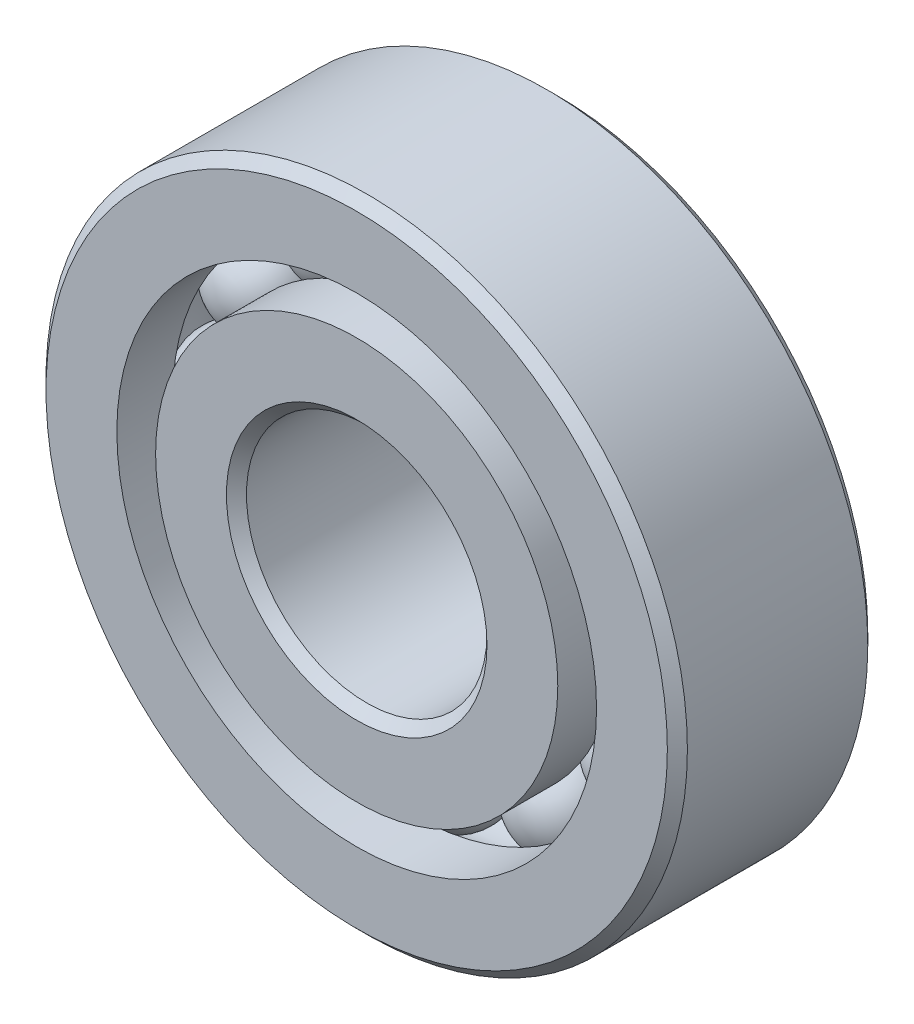
SolidWorks part; units mm, degrees
ref_plane "Front Plane" through (0, 0, 0) normal (0, 0, 1) x (1, 0, 0)
ref_plane "Top Plane" through (0, 0, 0) normal (0, 1, 0) x (1, 0, 0)
ref_plane "Right Plane" through (0, 0, 0) normal (1, 0, 0) x (0, 0, -1)
sketch "Sketch1" plane through (0, 0, 0) normal (1, 0, 0) x (0, 0, -1)
  line L0 (-1.9844, 0) -> (1.9844, 0) construction
  line L1 (0, 6.35) -> (0, -6.35) construction
  line L2 (1.7859, 6.35) -> (-1.7859, 6.35)
  line L3 (-1.7859, 6.35) -> (-1.9844, 6.1516)
  line L4 (-1.9844, 6.1516) -> (-1.9844, 4.7494)
  line L5 (-1.9844, 4.7494) -> (-0.8819, 4.7494)
  line L6 (1.9844, 4.7494) -> (0.8819, 4.7494)
  line L7 (1.9844, 6.1516) -> (1.9844, 4.7494)
  line L8 (1.7859, 6.35) -> (1.9844, 6.1516)
  line L9 (0, 6.35) -> (0, 4.3656) construction
  line L10 (0, 4.3656) -> (0, 2.3813) construction
  arc A0 (-0.8819, 4.7494) -> (0.8819, 4.7494) centre (0, 4.3656) cw
  point P14 (0, 2.3813)
  dimension "Width" = 3.9688
  dimension "OD" = 12.7
  dimension "D1" = 45
  dimension "D2" = 0.1984
  dimension "Shaft Dia" = 4.7625
  dimension "D3" = 1.7639
  dimension "D4" = 0.3838
revolve "Revolve1" add sketch "Sketch1" angle 360 about L0
sketch "Sketch3" plane through (0, 0, 0) normal (1, 0, 0) x (0, 0, -1)
  line L0 (-1.9844, 3.9818) -> (-0.8819, 3.9818)
  line L1 (0, 6.35) -> (0, -6.35) construction
  line L2 (-1.9844, 6.1516) -> (-1.9844, 4.7494) construction
  line L3 (-1.9844, 3.9818) -> (-1.9844, 2.5797)
  line L4 (-1.7859, 6.35) -> (-1.9844, 6.1516) construction
  line L5 (-1.9844, 2.5797) -> (-1.7859, 2.3813)
  line L6 (-1.7859, 2.3813) -> (1.7859, 2.3813)
  line L7 (1.7859, 6.35) -> (1.7859, -6.35) construction
  line L8 (1.7859, 2.3813) -> (1.9844, 2.5797)
  line L9 (1.9844, -6.1516) -> (1.9844, 6.1516) construction
  line L10 (1.9844, 2.5797) -> (1.9844, 3.9818)
  line L11 (1.9844, 3.9818) -> (0.8819, 3.9818)
  line L13 (1.7859, 6.35) -> (1.9844, 6.1516) construction
  arc A0 (0.8819, 4.7494) -> (-0.8819, 4.7494) centre (0, 4.3656) ccw construction
  arc A1 (0.8819, 3.9818) -> (-0.8819, 3.9818) centre (0, 4.3656) cw
revolve "Revolve3" add sketch "Sketch3" angle 360 about L0
sketch "Sketch4" plane through (0, 0, 0) normal (1, 0, 0) x (0, 0, -1)
  line L0 (-0.9618, 4.3656) -> (0.9618, 4.3656)
  arc A2 (-0.9618, 4.3656) -> (0.9618, 4.3656) centre (0, 4.3656) cw
  arc A3 (0.8819, 4.7494) -> (-0.8819, 4.7494) centre (0, 4.3656) ccw construction
revolve "Revolve4" add sketch "Sketch4" angle 360 about L0
ref_axis "Axis1" through (0, 0, -1.9844) along (0, 0, 1)
pattern_circular "CirPattern1" count 12 every 30 about axis through (0, 0, -1.9844) along (0, 0, 1) of bodies 104
equation "\"D2@Sketch1\" = \"Width@Sketch1\"*.05"
equation "\"D3@Sketch1\" = \"Width@Sketch1\"/2.25"
equation "\"D4@Sketch1\" = (((\"OD@Sketch1\"-\"Width@Sketch1\")/2)/3.25)/3.5"
equation "\"D2@CirPattern1\" = 360/\"Balls@CirPattern1\""
